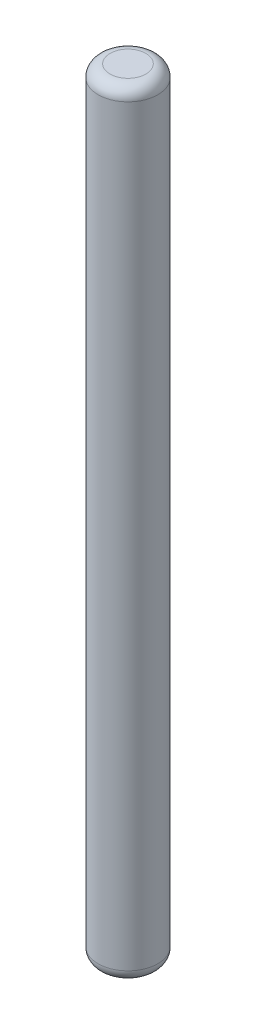
SolidWorks part; units mm, degrees
ref_plane "Front Plane" through (0, 0, 0) normal (0, 0, 1) x (1, 0, 0)
ref_plane "Top Plane" through (0, 0, 0) normal (0, 1, 0) x (1, 0, 0)
ref_plane "Right Plane" through (0, 0, 0) normal (1, 0, 0) x (0, 0, -1)
sketch "Sketch2" plane through (0, 0, 0) normal (0, 1, 0) x (1, 0, 0)
  circle A0 centre (0.0611, 0.0611) radius 2.5
  dimension "D1" = 5
extrude "Boss-Extrude1" add sketch "Sketch2" along normal blind 65
sketch "Sketch3" plane through (0, 65, 0) normal (0, 1, 0) x (1, 0, 0)
  line L0 (-1.0063, 2.3218) -> (1.1731, 2.3001)
  arc A0 (1.1731, 2.3001) -> (-1.0063, 2.3218) centre (0.0611, 0.0611) ccw
  circle A1 centre (0.0611, 0.0611) radius 2.5 construction
  dimension "D1" = 5
  dimension "D2" = 0
  dimension "D3" = 2.25
extrude "Cut-Extrude1" cut sketch "Sketch3" against normal blind 25
fillet "Fillet1" radius 1 1 edges at (0.0362, 65, 2.4388)
fillet "Fillet2" radius 1 1 edges at (0.0611, 0, 2.4389)
